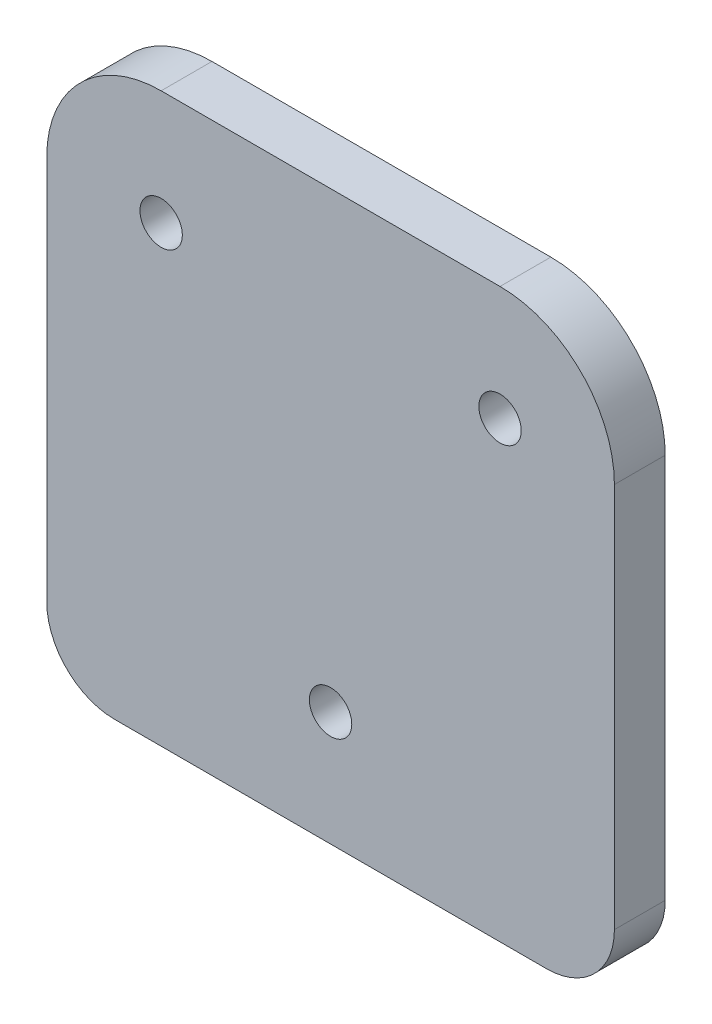
SolidWorks part; units mm, degrees
ref_plane "Plano frontal" through (0, 0, 0) normal (0, 0, 1) x (1, 0, 0)
ref_plane "Plano superior" through (0, 0, 0) normal (0, 1, 0) x (1, 0, 0)
ref_plane "Plano direito" through (0, 0, 0) normal (1, 0, 0) x (0, 0, -1)
sketch "Esboço1" plane through (0, 0, 0) normal (0, 0, 1) x (1, 0, 0)
  line L0 (-20, 33.5) -> (20, 33.5)
  line L1 (-20, 20) -> (20, 20) construction
  line L2 (-20, 20) -> (-20, -20) construction
  line L3 (-20, -20) -> (20, -20) construction
  line L4 (20, 20) -> (20, -20) construction
  line L5 (-20, 20) -> (20, -20) construction
  line L6 (-20, -20) -> (20, 20) construction
  line L9 (33.5, -20) -> (33.5, 20)
  line L10 (20, -33.5) -> (-20, -33.5)
  line L11 (-33.5, -20) -> (-33.5, 20)
  circle A0 centre (-20, 20) radius 2.5
  circle A1 centre (20, 20) radius 2.5
  circle A2 centre (0, -20) radius 2.5
  arc A3 (-20, 33.5) -> (-33.5, 20) centre (-20, 20) ccw
  arc A4 (33.5, 20) -> (20, 33.5) centre (20, 20) ccw
  arc A6 (20, -33.5) -> (33.5, -20) centre (20, -20) ccw
  arc A7 (-33.5, -20) -> (-20, -33.5) centre (-20, -20) ccw
  circle A8 centre (20, 20) radius 13.5 construction
  circle A9 centre (-20, 20) radius 13.5 construction
  point P0 (0, 0)
  point P13 (-8, 22)
  point P14 (0, -20)
  point P15 (32, 22)
  point P18 (12, -22)
  dimension "D3" = 5
  dimension "D1" = 40
  dimension "D2" = 40
  dimension "D4" = 11
extrude "Ressalto-extrusão1" add sketch "Esboço1" along normal blind 6
sketch "Esboço2" plane through (0, 0, 0) normal (0, 0, -1) x (-1, 0, 0)
  line L1 (-33.5, -20) -> (-20, -20)
  line L2 (-33.5, -20) -> (-33.5, -33.5)
  line L3 (-33.5, -33.5) -> (-20, -33.5)
  line L4 (-20, -20) -> (-20, -33.5)
  line L5 (33.5, -20) -> (20, -20)
  line L6 (33.5, -20) -> (33.5, -33.5)
  line L7 (33.5, -33.5) -> (20, -33.5)
  line L8 (20, -20) -> (20, -33.5)
  arc A0 (20, -33.5) -> (33.5, -20) centre (20, -20) ccw construction
extrude "Ressalto-extrusão2" add sketch "Esboço2" against normal up to surface (6 mm away) up to face at (22.5, 20, 6)
fillet "Filete1" radius 8 2 edges at (33.5, -33.5, 3) (-33.5, -33.5, 3)
ref_plane "Plano1" through (0, 0, 0) normal (-1, 0, 0) x (0, 0, 1)
